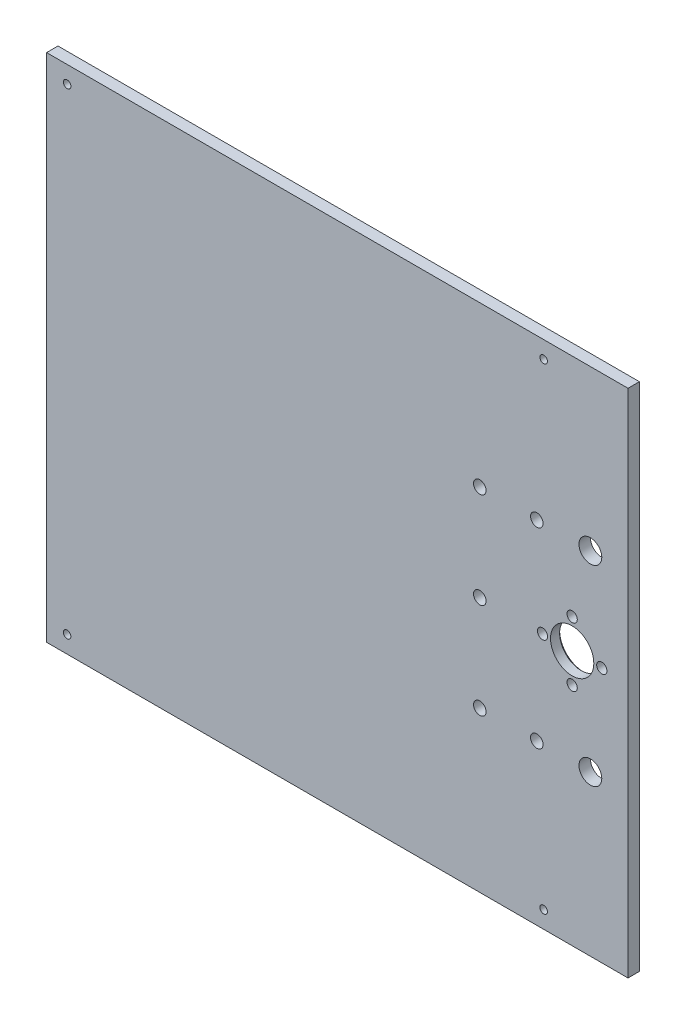
SolidWorks part; units mm, degrees
material "Lega 1060"
ref_plane "Piano frontale" through (0, 0, 0) normal (0, 0, 1) x (1, 0, 0)
ref_plane "Piano superiore" through (0, 0, 0) normal (0, 1, 0) x (1, 0, 0)
ref_plane "Piano destro" through (0, 0, 0) normal (1, 0, 0) x (0, 0, -1)
sketch "Schizzo1" plane through (0, 0, 0) normal (0, 0, 1) x (1, 0, 0)
  line L1 (0, 20) -> (-255, 20)
  line L2 (0, 20) -> (0, 244)
  line L3 (0, 244) -> (-255, 244)
  line L4 (-255, 20) -> (-255, 244)
  dimension "D1" = 255
  dimension "D2" = 224
  dimension "D3" = 20
extrude "Estrusione-Estrusione1" add sketch "Schizzo1" along normal blind 5
sketch "Schizzo2" plane through (0, 0, 0) normal (0, 0, -1) x (-1, 0, 0)
  circle A0 centre (24.5, 132) radius 9.5
  dimension "D1" = 19
extrude "Taglio-Estrusione1" cut sketch "Schizzo2" against normal up to next
chamfer "Smusso1" distance 1 angle 45 1 edges at (-34, 132, 0)
hole_wizard "Foro per Vite M4-1" positions "Schizzo4" profile "Schizzo3" hole size "M4" standard "ISO"
sketch "Schizzo4" plane through (0, 0, 0) normal (0, 0, -1) x (-1, 0, 0)
  line L0 (24.5, 145) -> (24.5, 119) construction
  point P0 (24.5, 119)
  point P3 (37.5, 132)
  point P6 (24.5, 145)
  point P9 (11.5, 132)
sketch "Schizzo3" plane through (-24.5, 119, 0) normal (1, 0, 0) x (0, 1, 0)
  line L0 (0, 0) -> (0, 9.3519)
  line L1 (0, 9.3519) -> (2.25, 8)
  line L2 (2.25, 8) -> (2.25, 0)
  line L5 (2.25, 0) -> (0, 0)
  line L10 (0, 9.3519) -> (-2.25, 8) construction
  line L11 (0, -6.35) -> (0, 107.95) construction
  dimension "Hole Dia." = 4.5
  dimension "Hole Depth" = 8
  dimension "Drill Angle" = 118
sketch "Schizzo6" plane through (0, 0, 5) normal (0, 0, 1) x (1, 0, 0)
  circle A0 centre (-16.5, 90) radius 5
  circle A1 centre (-16.5, 174) radius 5
  dimension "D1" = 10
  dimension "D2" = 10
extrude "Taglio-Estrusione2" cut sketch "Schizzo6" against normal up to next
hole_wizard "Foro per Vite M5-2" positions "Schizzo8" profile "Schizzo7" hole size "M5" standard "ISO" end condition up to next
sketch "Schizzo8" plane through (0, 0, 5) normal (0, 0, 1) x (1, 0, 0)
  line L2 (0, 244) -> (-255, 244) construction
  line L3 (0, 20) -> (0, 244) construction
  line L4 (-89.6625, 132) -> (-52.1719, 132) construction
  point P0 (-27.953, 298.6689)
  point P1 (-40, 90)
  point P3 (-65, 132)
  point P5 (-40, 174)
  point P27 (-65, 174)
  point P29 (-65, 90)
  dimension "D1" = 25
  dimension "D2" = 42
  dimension "D3" = 42
  dimension "D4" = 112
  dimension "D5" = 65
  dimension "D6" = 42
  dimension "D7" = 65
sketch "Schizzo7" plane through (-27.953, 298.6689, 5) normal (1, 0, 0) x (0, -1, 0)
  line L0 (0, 0) -> (0, 5)
  line L1 (0, 5) -> (2.75, 5)
  line L2 (2.75, 5) -> (2.75, 0)
  line L5 (2.75, 0) -> (0, 0)
  line L11 (0, -6.35) -> (0, 107.95) construction
  dimension "Thru Hole Dia." = 5.5
  dimension "Thru Hole Depth" = 5
hole_wizard "Foro filettato M4-1" positions "Schizzo11" profile "Schizzo10" tap size "M4" standard "ISO" end condition up to next
sketch "Schizzo11" plane through (0, 0, 0) normal (0, 0, -1) x (-1, 0, 0)
  line L0 (255, 20) -> (0, 20) construction
  point P0 (246, 27.5)
  point P2 (37, 27.5)
  point P4 (246, 236.5)
  point P6 (37, 236.5)
  dimension "D1" = 7.5
  dimension "D2" = 209
  dimension "D3" = 209
  dimension "D4" = 9
sketch "Schizzo10" plane through (-246, 27.5, 0) normal (1, 0, 0) x (0, 1, 0)
  line L0 (0, 0) -> (0, 5)
  line L1 (0, 5) -> (1.65, 5)
  line L2 (1.65, 5) -> (1.65, 0)
  line L5 (1.65, 0) -> (0, 0)
  line L11 (0, -6.35) -> (0, 107.95) construction
  dimension "Thru Tap Drill Dia." = 3.3
  dimension "Thru Tap Drill Depth" = 5
cosmetic thread "Filettatura del foro2" parameters "D2"=4
cosmetic thread "Filettatura del foro4" parameters "D2"=4
cosmetic thread "Filettatura del foro5" parameters "D2"=4
cosmetic thread "Filettatura del foro6" parameters "D2"=4
